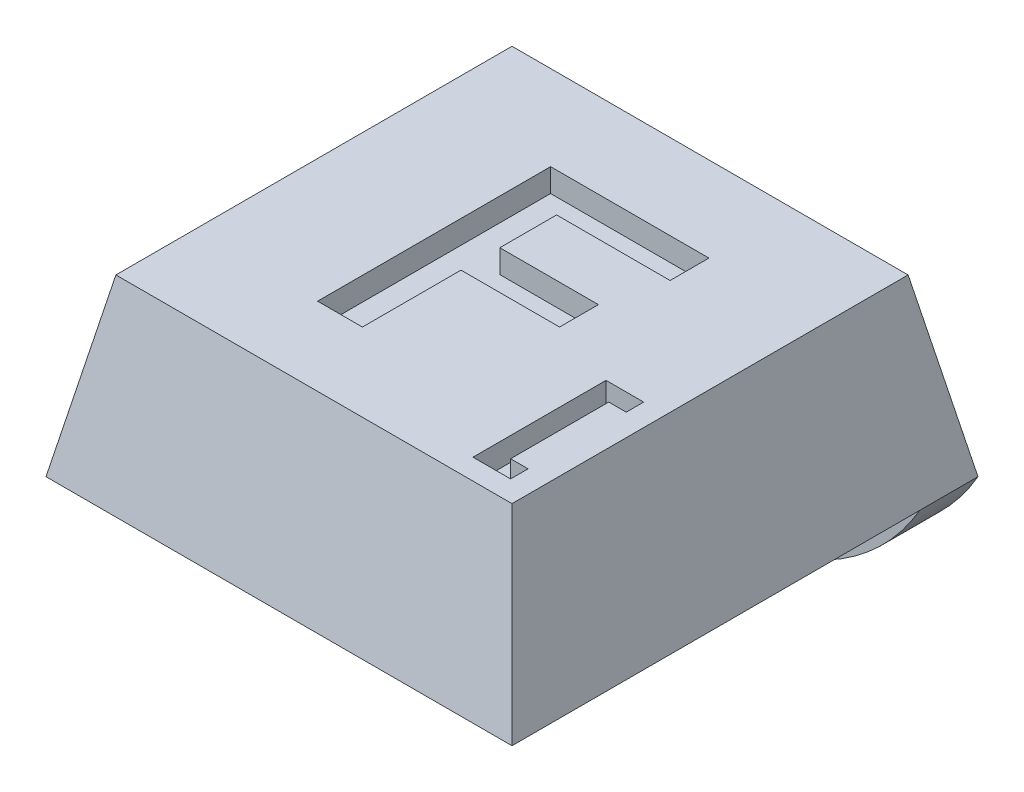
SolidWorks part; units mm, degrees
ref_plane "Front Plane" through (0, 0, 0) normal (0, 0, 1) x (1, 0, 0)
ref_plane "Top Plane" through (0, 0, 0) normal (0, 1, 0) x (1, 0, 0)
ref_plane "Right Plane" through (0, 0, 0) normal (1, 0, 0) x (0, 0, -1)
sketch "Sketch1" plane through (0, 0, 0) normal (0, 1, 0) x (1, 0, 0)
  line L1 (0, 0) -> (8, 0)
  line L2 (0, 0) -> (0, 8)
  line L3 (0, 8) -> (8, 8)
  line L4 (8, 0) -> (8, 8)
  dimension "D1" = 8
  dimension "D2" = 8
extrude "Boss-Extrude1" add sketch "Sketch1" along normal blind 3
sketch "Sketch2" plane through (0, 0, 0) normal (0, 0, 1) x (1, 0, 0)
  line L0 (0, 0) -> (0.6, 3)
  line L1 (0, 3) -> (8, 3) construction
  line L2 (0.6, 3) -> (0, 3)
  line L3 (0, 3) -> (0, 0)
  line L4 (8, 0) -> (7.4, 3)
  line L5 (7.4, 3) -> (8, 3)
  line L6 (8, 3) -> (8, 0)
  dimension "D1" = 0.6
  dimension "D2" = 0.6
extrude "Cut-Extrude1" cut sketch "Sketch2" against normal through all both and the other way through all
sketch "Sketch3" plane through (0, 0, 0) normal (1, 0, 0) x (0, 0, -1)
  line L0 (0, 0) -> (0.6, 3)
  line L1 (8, 3) -> (0, 3) construction
  line L2 (0.6, 3) -> (0, 3)
  line L3 (0, 3) -> (0, 0)
  line L4 (8, 3) -> (7.4, 3)
  line L5 (7.4, 3) -> (8, 0)
  line L6 (8, 3) -> (8, 0)
  dimension "D1" = 0.6
  dimension "D2" = 0.6
extrude "Cut-Extrude2" cut sketch "Sketch3" along normal blind 11
sketch "Sketch4" plane through (0, 0, 0) normal (0, -1, 0) x (1, 0, 0)
  line L0 (8, 0) -> (8, -8) construction
  line L3 (0, 0) -> (8, 0) construction
  circle A0 centre (4, -3.75) radius 1.8
  dimension "D1" = 3.6
  dimension "D2" = 4
  dimension "D3" = 3.75
extrude "Cut-Extrude3" cut sketch "Sketch4" against normal blind 0.8
sketch "Sketch5" plane through (0, 0, 0) normal (0, -1, 0) x (1, 0, 0)
  line L0 (8, 0) -> (8, -8) construction
  line L1 (0, -8) -> (8, -8)
  line L2 (0, -8) -> (0, -7)
  line L3 (0, -7) -> (8, -7)
  line L4 (8, -8) -> (8, -7)
  dimension "D1" = 1
extrude "Boss-Extrude2" add sketch "Sketch5" along normal blind 2
fillet "Fillet1" radius 4 2 edges at (8, -2, -7.5) (0, -2, -7.5)
sketch "Sketch6" plane through (0, 3, 0) normal (0, 1, 0) x (1, 0, 0)
  text T0 "F" font "Arial" height 4
extrude "Cut-Extrude4" cut sketch "Sketch6" against normal blind 0.4
sketch "Sketch7" plane through (0, 3, 0) normal (0, 1, 0) x (1, 0, 0)
  text T0 "[" font "Arial" height 1.8
extrude "Cut-Extrude5" cut sketch "Sketch7" against normal blind 0.4
